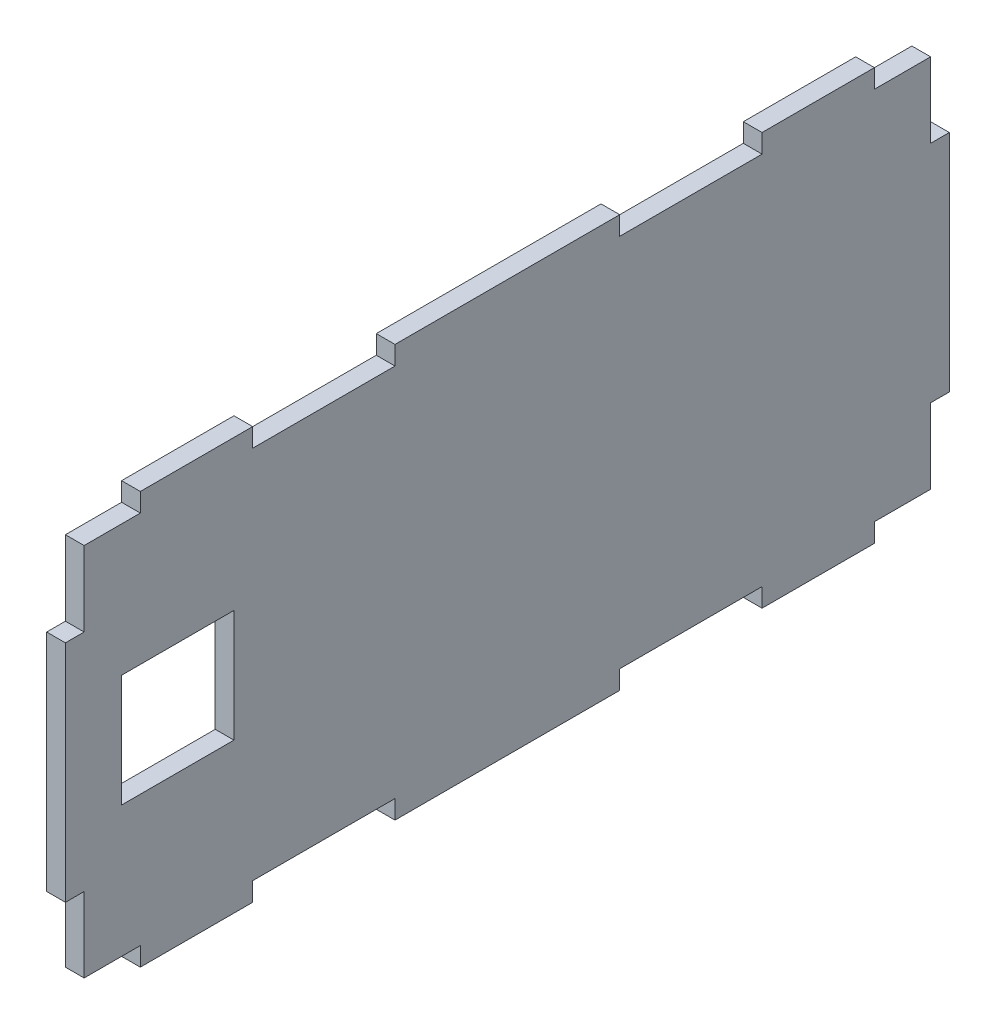
SolidWorks part; units mm, degrees
ref_plane "Front Plane" through (0, 0, 0) normal (0, 0, 1) x (1, 0, 0)
ref_plane "Top Plane" through (0, 0, 0) normal (0, 1, 0) x (1, 0, 0)
ref_plane "Right Plane" through (0, 0, 0) normal (1, 0, 0) x (0, 0, -1)
sketch "Sketch1" plane through (0, 0, 0) normal (1, 0, 0) x (0, 0, -1)
  line L0 (-113, 0) -> (113, 0) construction
  line L1 (113, -50) -> (-113, -50)
  line L2 (113, -50) -> (113, 50)
  line L3 (113, 50) -> (-113, 50)
  line L4 (-113, -50) -> (-113, 50)
  line L5 (113, -50) -> (-113, 50) construction
  line L6 (113, 50) -> (-113, -50) construction
  line L7 (0, -50) -> (0, 50) construction
  line L8 (113, -30) -> (118, -30)
  line L9 (98, 50) -> (68, 50)
  line L10 (98, 50) -> (98, 55)
  line L11 (98, 55) -> (68, 55)
  line L12 (68, 50) -> (68, 55)
  line L13 (0, 50) -> (30, 50)
  line L14 (0, 50) -> (0, 55)
  line L15 (-30, 55) -> (30, 55)
  line L16 (30, 50) -> (30, 55)
  line L17 (113, 0) -> (118, 0)
  line L18 (113, 0) -> (113, 30)
  line L19 (113, 30) -> (118, 30)
  line L20 (118, -30) -> (118, 30)
  line L21 (98, -50) -> (98, -55)
  line L22 (68, -50) -> (68, -55)
  line L23 (98, -55) -> (68, -55)
  line L24 (30, -50) -> (30, -55)
  line L25 (-30, -55) -> (30, -55)
  line L26 (-30, -50) -> (-30, -55)
  line L27 (-68, -50) -> (-68, -55)
  line L28 (-98, -50) -> (-98, -55)
  line L29 (-98, -55) -> (-68, -55)
  line L30 (-113, -30) -> (-118, -30)
  line L31 (-118, -30) -> (-118, 30)
  line L32 (-113, 30) -> (-118, 30)
  line L33 (-98, 50) -> (-98, 55)
  line L34 (-68, 50) -> (-68, 55)
  line L35 (-98, 55) -> (-68, 55)
  line L36 (-30, 50) -> (-30, 55)
  line L37 (30, 50) -> (-30, 50)
  line L38 (-68, 50) -> (-98, 50)
  line L39 (-113, 30) -> (-113, -30)
  line L40 (-98, -50) -> (-68, -50)
  line L41 (-30, -50) -> (30, -50)
  line L42 (68, -50) -> (98, -50)
  line L43 (113, -30) -> (113, 30)
  line L44 (98, 50) -> (68, 50)
  line L46 (-103, -15) -> (-73, -15)
  line L47 (-103, -15) -> (-103, 15)
  line L48 (-103, 15) -> (-73, 15)
  line L49 (-73, -15) -> (-73, 15)
  point P0 (0, 0)
  point P17 (98, 52.5)
  point P32 (0, -55)
  dimension "D1" = 226
  dimension "D2" = 100
  dimension "D3" = 5
  dimension "D4" = 5
  dimension "D5" = 15
  dimension "D6" = 30
  dimension "D7" = 30
  dimension "D8" = 5
  dimension "D9" = 30
  dimension "D10" = 10
  dimension "D11" = 30
  dimension "D12" = 35
  dimension "D13" = 35
  dimension "D14" = 30
extrude "Boss-Extrude1" add sketch "Sketch1" along normal blind 5 contours L4 L1 L2 L3 | L35 L33 L3 L34 | L28 L29 L27 L1 | L4 L32 L31 L30 | L12 L3 L10 L11 | L37 L36 L15 L16 | L25 L24 L41 L26 | L23 L22 L42 L21 | L43 L8 L20 L19 region at (0, 0, -3.6498) region at (0, -52.5, 83) region at (0, 52.5, -83) region at (0, 0, 115.5) region at (0, 52.5, 83)
